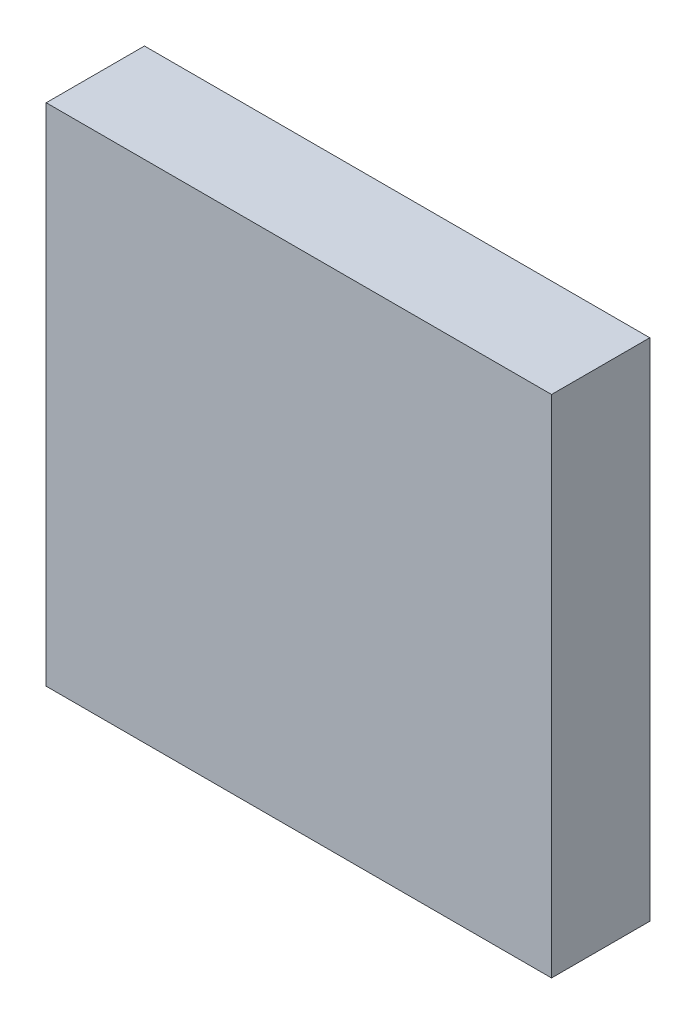
SolidWorks part; units mm, degrees
ref_plane "Front Plane" through (0, 0, 0) normal (0, 0, 1) x (1, 0, 0)
ref_plane "Top Plane" through (0, 0, 0) normal (0, 1, 0) x (1, 0, 0)
ref_plane "Right Plane" through (0, 0, 0) normal (1, 0, 0) x (0, 0, -1)
sketch "Sketch1" plane through (0, 0, 0) normal (0, 0, 1) x (1, 0, 0)
  line L1 (-18, -18) -> (18, -18)
  line L2 (-18, -18) -> (-18, 18)
  line L3 (-18, 18) -> (18, 18)
  line L4 (18, -18) -> (18, 18)
  line L5 (-18, -18) -> (18, 18) construction
  line L6 (-18, 18) -> (18, -18) construction
  line L7 (-15.5, -15.5) -> (15.5, -15.5)
  line L8 (-15.5, -15.5) -> (-15.5, 15.5)
  line L9 (-15.5, 15.5) -> (15.5, 15.5)
  line L10 (15.5, -15.5) -> (15.5, 15.5)
  line L11 (-15.5, -15.5) -> (15.5, 15.5) construction
  line L12 (-15.5, 15.5) -> (15.5, -15.5) construction
  circle A0 centre (-15.5, 15.5) radius 2.15
  circle A1 centre (15.5, 15.5) radius 2.15
  circle A2 centre (15.5, -15.5) radius 2.15
  circle A3 centre (-15.5, -15.5) radius 2.15
  point P0 (0, 0)
  point P6 (0, 0)
  dimension "D5" = 4.3
  dimension "D6" = 4.3
  dimension "D7" = 4.3
  dimension "D8" = 4.3
  dimension "D1" = 36
  dimension "D2" = 36
  dimension "D3" = 31
  dimension "D4" = 31
extrude "Boss-Extrude1" add sketch "Sketch1" along normal mid plane 6 contours L1 L4 L3 L2 A3 L8 A0 L9 A1 L10 A2 L7 | A3 L7 A2 L10 A1 L9 A0 L8 region at (-17.4909, 0, 0) region at (0, 0, 0)
extrude "Boss-Extrude2" add sketch "Sketch1<3>" along normal mid plane 2 from surface contours L1 L4 L3 L2 A3 L8 A0 L9 A1 L10 A2 L7 | L10 A1 L9 | L9 A0 L8 | L7 A2 L10 | L9 A1 L10 | L8 A0 L9 | L10 A2 L7 | L8 A3 L7 | L7 A3 L8 | A3 L7 A2 L10 A1 L9 A0 L8 region at (-17.4909, 0, 0) region at (-14.5875, -14.5875, 0) region at (-15.8042, -15.8042, 0) region at (0, 0, 0) region at (14.5875, -14.5875, 0) region at (15.8042, -15.8042, 0) region at (-15.8042, 15.8042, 0) region at (-14.5875, 14.5875, 0) region at (14.5875, 14.5875, 0) region at (15.8042, 15.8042, 0) starting at face at (-13.35, 15.5, 3)
sketch "Sketch1<3>" plane through (0, 0, 0) normal (0, 0, 1) x (1, 0, 0) same geometry as "Sketch1"
